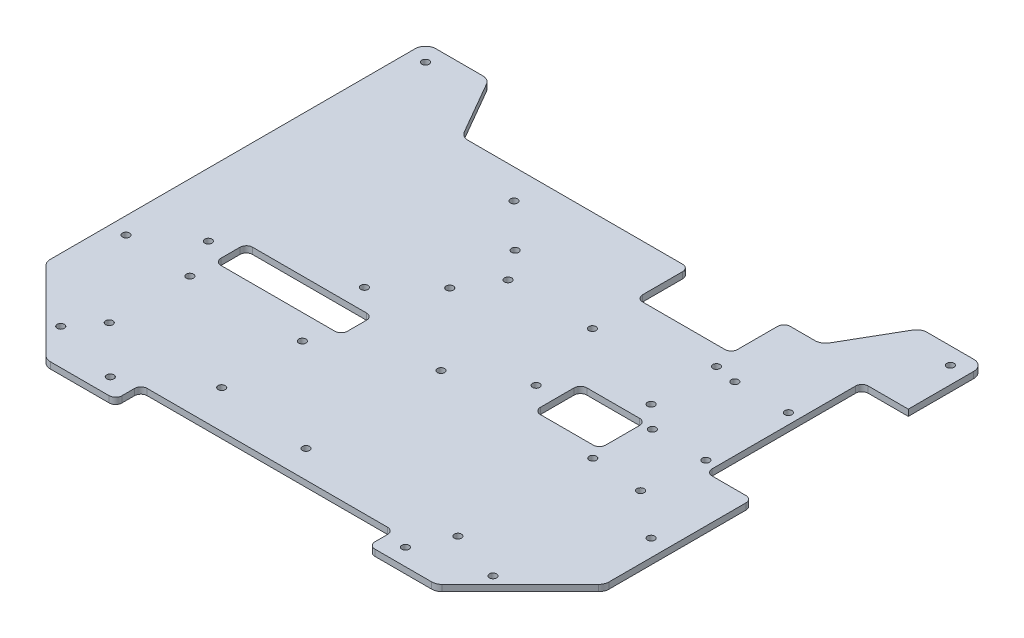
SolidWorks part; units mm, degrees
material "Acier non allié"
ref_plane "Front" through (0, 0, 0) normal (0, 0, 1) x (1, 0, 0)
ref_plane "Top" through (0, 0, 0) normal (0, 1, 0) x (1, 0, 0)
ref_plane "Right" through (0, 0, 0) normal (1, 0, 0) x (0, 0, -1)
sketch "Esquisse1" plane through (0, 0, 0) normal (0, 1, 0) x (1, 0, 0)
  line L0 (0, 0) -> (0, 190) construction
  line L1 (-92.5, 0) -> (92.5, 0)
  line L2 (92.5, 0) -> (132.5, 40)
  line L3 (132.5, 40) -> (132.5, 220)
  line L4 (132.5, 220) -> (102.5, 220)
  line L5 (102.5, 220) -> (85.1795, 190)
  line L6 (85.1795, 190) -> (-85.1795, 190)
  line L7 (-102.5, 220) -> (-85.1795, 190)
  line L8 (-132.5, 220) -> (-102.5, 220)
  line L9 (-132.5, 40) -> (-132.5, 220)
  line L10 (-92.5, 0) -> (-132.5, 40)
  dimension "D1" = 132.5
  dimension "D2" = 220
  dimension "D3" = 60
  dimension "D4" = 30
  dimension "D5" = 40
  dimension "D6" = 40
  dimension "D7" = 30
extrude "Boss.-Extru.1" add sketch "Esquisse1" along normal blind 3
fillet "Congé1" radius 5 10 edges at (92.5, 1.5, 0) (132.5, 1.5, -40) (132.5, 1.5, -220) (102.5, 1.5, -220) (85.1795, 1.5, -190) (-85.1795, 1.5, -190) (-102.5, 1.5, -220) (-132.5, 1.5, -220) (-92.5, 1.5, 0) (-132.5, 1.5, -40)
sketch "Esquisse2" plane through (0, 3, 0) normal (0, 1, 0) x (1, 0, 0)
  line L0 (0, 0) -> (0, 294.1173) construction
  line L2 (-90.4289, 0) -> (90.4289, 0) construction
  circle A0 centre (70, 8) radius 1
  circle A1 centre (124.5, 70) radius 1
  circle A2 centre (124.5, 212) radius 1
  circle A3 centre (-124.5, 212) radius 1
  circle A4 centre (-124.5, 70) radius 1
  circle A5 centre (-70, 8) radius 1
  dimension "D2" = 2
  dimension "D6" = 2
  dimension "D9" = 2
  dimension "D1" = 70
  dimension "D3" = 8
  dimension "D4" = 124.5
  dimension "D5" = 70
  dimension "D7" = 124.5
  dimension "D8" = 212
extrude "Enlèv. mat.-Extru.1" cut sketch "Esquisse2" against normal blind 3
hole_wizard "Dégagement M31" positions "Esquisse3" profile "Esquisse4" hole size "M3" standard "ISO" end condition through all
sketch "Esquisse3" plane through (0, 3, 0) normal (0, 1, 0) x (1, 0, 0)
  point P0 (70, 8)
  point P3 (-70, 8)
  point P6 (-124.5, 70)
  point P9 (-124.5, 212)
  point P12 (124.5, 212)
  point P15 (124.5, 70)
sketch "Esquisse4" plane through (70, 3, -8) normal (1, 0, 0) x (0, 0, 1)
  line L0 (0, 0) -> (0, 3)
  line L1 (0, 3) -> (1.7, 3)
  line L2 (1.7, 3) -> (1.7, 0)
  line L5 (1.7, 0) -> (0, 0)
  line L11 (0, -6.35) -> (0, 107.95) construction
  dimension "Diamètre du perçage jusqu'au prochain" = 3.4
  dimension "Profondeur du perçage jusqu'au prochain" = 3
sketch "Esquisse5" plane through (0, 3, 0) normal (0, 1, 0) x (1, 0, 0)
  line L0 (82.2927, 190) -> (-82.2927, 190) construction
  line L1 (67.5, 190) -> (22.5, 190)
  line L2 (67.5, 190) -> (67.5, 165)
  line L3 (67.5, 165) -> (22.5, 165)
  line L4 (22.5, 190) -> (22.5, 165)
  line L5 (132.5, 42.0711) -> (132.5, 215) construction
  line L6 (132.5, 184) -> (110.5, 184)
  line L7 (132.5, 184) -> (132.5, 110)
  line L8 (132.5, 110) -> (110.5, 110)
  line L9 (110.5, 184) -> (110.5, 110)
  line L10 (127.5, 220) -> (105.3868, 220) construction
  dimension "D1" = 25
  dimension "D2" = 65
  dimension "D3" = 110
  dimension "D4" = 36
  dimension "D5" = 110
  dimension "D6" = 22
extrude "Enlèv. mat.-Extru.2" cut sketch "Esquisse5" against normal through all
fillet "Congé2" radius 3 7 edges at (132.5, 1.5, -110) (110.5, 1.5, -110) (110.5, 1.5, -184) (67.5, 1.5, -190) (67.5, 1.5, -165) (22.5, 1.5, -165) (22.5, 1.5, -190)
sketch "Esquisse6" plane through (0, 3, 0) normal (0, 1, 0) x (1, 0, 0)
  line L0 (110.5, 140.5) -> (-167.6757, 140.5) construction
  line L1 (110.5, 181) -> (110.5, 113) construction
  line L2 (-90.4289, 0) -> (90.4289, 0) construction
  line L3 (110.5, 181) -> (110.5, 113) construction
  circle A0 centre (69.5, 156) radius 1
  circle A1 centre (-26, 156) radius 1
  circle A2 centre (-46.5, 176) radius 1
  circle A3 centre (69.5, 125) radius 1
  circle A4 centre (-26, 125) radius 1
  circle A5 centre (-46.5, 105) radius 1
  dimension "D4" = 2
  dimension "D6" = 2
  dimension "D10" = 2
  dimension "D1" = 140.5
  dimension "D2" = 41
  dimension "D3" = 15.5
  dimension "D5" = 136.5
  dimension "D7" = 15.5
  dimension "D8" = 35.5
  dimension "D9" = 157
extrude "Enlèv. mat.-Extru.3" cut sketch "Esquisse6" against normal through all
hole_wizard "Dégagement M32" positions "Esquisse7" profile "Esquisse8" hole size "M3" standard "ISO"
sketch "Esquisse7" plane through (0, 3, 0) normal (0, 1, 0) x (1, 0, 0)
  point P0 (-46.5, 105)
  point P3 (-26, 125)
  point P6 (-26, 156)
  point P9 (-46.5, 176)
  point P12 (69.5, 156)
  point P15 (69.5, 125)
sketch "Esquisse8" plane through (-46.5, 3, -105) normal (1, 0, 0) x (0, 0, 1)
  line L0 (0, 0) -> (0, 11.0215)
  line L1 (0, 11.0215) -> (1.7, 10)
  line L2 (1.7, 10) -> (1.7, 0)
  line L5 (1.7, 0) -> (0, 0)
  line L10 (0, 11.0215) -> (-1.7, 10) construction
  line L11 (0, -6.35) -> (0, 107.95) construction
  dimension "Diamètre du perçage" = 3.4
  dimension "Profondeur du perçage" = 10
  dimension "Angle de pointe" = 118
sketch "Esquisse9" plane through (0, 3, 0) normal (0, 1, 0) x (1, 0, 0)
  line L0 (132.5, 42.0711) -> (132.5, 107) construction
  line L1 (-90.4289, 0) -> (90.4289, 0) construction
  line L2 (-132.5, 215) -> (-132.5, 42.0711) construction
  line L3 (-39.16, 30) -> (-92.5, 30) construction
  line L4 (-39.16, 30) -> (-39.16, 68.24) construction
  line L5 (-39.16, 68.24) -> (-92.5, 68.24) construction
  line L6 (-92.5, 30) -> (-92.5, 68.24) construction
  line L7 (5.84, 25) -> (5.84, 89) construction
  line L8 (25.5, 165) -> (64.5, 165) construction
  line L9 (24.5, 142.1606) -> (-15.5, 142.1606) construction
  line L10 (110.5, 181) -> (110.5, 113) construction
  line L11 (113.5, 110) -> (129.5, 110) construction
  circle A0 centre (105.5, 115) radius 1
  circle A3 centre (105.5, 154.12) radius 1
  circle A6 centre (-92.5, 68.24) radius 1
  circle A7 centre (-39.16, 68.24) radius 1
  circle A8 centre (-39.16, 30) radius 1
  circle A9 centre (-92.5, 30) radius 1
  circle A10 centre (5.84, 89) radius 1
  circle A11 centre (77.84, 89) radius 1
  circle A12 centre (5.84, 25) radius 1
  circle A13 centre (77.84, 25) radius 1
  circle A14 centre (-15.5, 142.1606) radius 1
  circle A15 centre (24.5, 142.1606) radius 1
  circle A16 centre (34.5, 105.5) radius 1
  circle A17 centre (80.1, 115) radius 1
  circle A18 centre (80.1, 154.12) radius 1
  dimension "D2" = 2
  dimension "D4" = 2
  dimension "D17" = 2
  dimension "D18" = 2
  dimension "D19" = 2
  dimension "D20" = 2
  dimension "D21" = 2
  dimension "D22" = 2
  dimension "D23" = 2
  dimension "D24" = 2
  dimension "D32" = 2
  dimension "D33" = 2
  dimension "D34" = 2
  dimension "D11" = 2
  dimension "D12" = 2
  dimension "D5" = 27
  dimension "25" = 27
  dimension "D10" = 39.12
  dimension "D13" = 38.24
  dimension "D14" = 53.34
  dimension "D15" = 30
  dimension "D16" = 40
  dimension "D25" = 72
  dimension "D26" = 72
  dimension "D27" = 64
  dimension "D28" = 64
  dimension "D29" = 45
  dimension "D30" = 25
  dimension "D31" = 25
  dimension "D36" = 38
  dimension "D37" = 40
  dimension "D39" = 10
  dimension "D7" = 5
  dimension "D8" = 25.4
  dimension "D9" = 25.4
  dimension "D40" = 39.12
  dimension "D35" = 59.5
  dimension "D38" = 76
extrude "Enlèv. mat.-Extru.4" cut sketch "Esquisse9" against normal through all
hole_wizard "Dégagement M33" positions "Esquisse10" profile "Esquisse11" hole size "M3" standard "ISO"
sketch "Esquisse10" plane through (0, 3, 0) normal (0, 1, 0) x (1, 0, 0)
  point P3 (105.5, 115)
  point P9 (105.5, 154.12)
  point P14 (80.1, 154.12)
  point P17 (80.1, 115)
sketch "Esquisse11" plane through (105.5, 3, -115) normal (1, 0, 0) x (0, 0, 1)
  line L0 (0, 0) -> (0, 11.0215)
  line L1 (0, 11.0215) -> (1.7, 10)
  line L2 (1.7, 10) -> (1.7, 0)
  line L5 (1.7, 0) -> (0, 0)
  line L10 (0, 11.0215) -> (-1.7, 10) construction
  line L11 (0, -6.35) -> (0, 107.95) construction
  dimension "Diamètre du perçage" = 3.4
  dimension "Profondeur du perçage" = 10
  dimension "Angle de pointe" = 118
sketch "Esquisse12" plane through (0, 3, 0) normal (0, 1, 0) x (1, 0, 0)
  line L2 (-90.4289, 0) -> (90.4289, 0) construction
  line L3 (102.5, 17) -> (-102.5, 17) construction
  line L4 (102.5, 17) -> (102.5, 87) construction
  line L5 (102.5, 87) -> (-102.5, 87) construction
  line L6 (-102.5, 17) -> (-102.5, 87) construction
  line L7 (132.5, 42.0711) -> (132.5, 107) construction
  circle A4 centre (-102.5, 87) radius 1
  circle A5 centre (102.5, 87) radius 1
  circle A6 centre (102.5, 17) radius 1
  circle A7 centre (-102.5, 17) radius 1
  point P6 (102.5, 52)
  dimension "D5" = 2
  dimension "D6" = 2
  dimension "D7" = 2
  dimension "D8" = 2
  dimension "D1" = 70
  dimension "D2" = 205
  dimension "D3" = 17
  dimension "D4" = 30
extrude "Enlèv. mat.-Extru.5" cut sketch "Esquisse12" against normal through all and the other way through all
hole_wizard "Dégagement M34" positions "Esquisse13" profile "Esquisse14" hole size "M3" standard "ISO"
sketch "Esquisse13" plane through (0, 3, 0) normal (0, 1, 0) x (1, 0, 0)
  point P3 (-92.5, 68.24)
  point P6 (-92.5, 30)
  point P9 (-39.16, 30)
  point P12 (-39.16, 68.24)
  point P16 (5.84, 25)
  point P19 (77.84, 25)
  point P22 (5.84, 89)
  point P25 (77.84, 89)
  point P29 (34.5, 105.5)
  point P32 (24.5, 142.1606)
  point P35 (-15.5, 142.1606)
sketch "Esquisse14" plane through (-92.5, 3, -68.24) normal (1, 0, 0) x (0, 0, 1)
  line L0 (0, 0) -> (0, 11.0215)
  line L1 (0, 11.0215) -> (1.7, 10)
  line L2 (1.7, 10) -> (1.7, 0)
  line L5 (1.7, 0) -> (0, 0)
  line L10 (0, 11.0215) -> (-1.7, 10) construction
  line L11 (0, -6.35) -> (0, 107.95) construction
  dimension "Diamètre du perçage" = 3.4
  dimension "Profondeur du perçage" = 10
  dimension "Angle de pointe" = 118
hole_wizard "Dégagement M35" positions "Esquisse15" profile "Esquisse16" hole size "M3" standard "ISO"
sketch "Esquisse15" plane through (0, 3, 0) normal (0, 1, 0) x (1, 0, 0)
  point P0 (-102.5, 17)
  point P3 (-102.5, 87)
  point P6 (102.5, 87)
  point P9 (102.5, 17)
sketch "Esquisse16" plane through (-102.5, 3, -17) normal (1, 0, 0) x (0, 0, 1)
  line L0 (0, 0) -> (0, 11.0215)
  line L1 (0, 11.0215) -> (1.7, 10)
  line L2 (1.7, 10) -> (1.7, 0)
  line L5 (1.7, 0) -> (0, 0)
  line L10 (0, 11.0215) -> (-1.7, 10) construction
  line L11 (0, -6.35) -> (0, 107.95) construction
  dimension "Diamètre du perçage" = 3.4
  dimension "Profondeur du perçage" = 10
  dimension "Angle de pointe" = 118
sketch "Esquisse17" plane through (0, 3, 0) normal (0, 1, 0) x (1, 0, 0)
  line L0 (-90.4289, 0) -> (90.4289, 0) construction
  line L1 (-92.5, 95) -> (-32.5, 95)
  line L2 (-92.5, 95) -> (-92.5, 80)
  line L3 (-92.5, 80) -> (-32.5, 80)
  line L4 (-32.5, 95) -> (-32.5, 80)
  line L5 (-132.5, 215) -> (-132.5, 42.0711) construction
  line L6 (132.5, 42.0711) -> (132.5, 107) construction
  line L7 (44.5, 116.5) -> (75.5, 116.5)
  line L8 (44.5, 116.5) -> (44.5, 94.5)
  line L9 (44.5, 94.5) -> (75.5, 94.5)
  line L10 (75.5, 116.5) -> (75.5, 94.5)
  line L11 (82.2927, 190) -> (70.5, 190) construction
  line L13 (-59.5, 12) -> (60.5, 12)
  line L14 (-59.5, 12) -> (-59.5, 0)
  line L15 (-59.5, 0) -> (60.5, 0)
  line L16 (60.5, 12) -> (60.5, 0)
  dimension "D1" = 60
  dimension "D2" = 15
  dimension "D3" = 80
  dimension "D4" = 40
  dimension "D5" = 31
  dimension "D6" = 22
  dimension "D7" = 57
  dimension "D8" = 73.5
  dimension "D9" = 12
  dimension "D11" = 120
  dimension "D12" = 72
extrude "Enlèv. mat.-Extru.6" cut sketch "Esquisse17" against normal up to surface (3 mm away) up to face at (-102.5, 0, -15.3)
fillet "Congé3" radius 3 12 edges at (60.5, 1.5, 0) (60.5, 1.5, -12) (-59.5, 1.5, -12) (-59.5, 1.5, 0) (44.5, 1.5, -116.5) (75.5, 1.5, -116.5) (75.5, 1.5, -94.5) (44.5, 1.5, -94.5) (-92.5, 1.5, -80) (-32.5, 1.5, -80) (-32.5, 1.5, -95) (-92.5, 1.5, -95)
equation "\"WIDTH\"= 300mm'Total width of the robot"
equation "\"LENGTH\"= 220mm'Total length of the robot"
equation "\"CUT_DEPTH\"= 45mm'Depth of the cut on the edges of the plate"
equation "\"Plate_th\"= 3mm'Thickness of the plate"
equation "\"D1\"= \"Plate_th\""
equation "\"D5@Esquisse9\"=\"25@Esquisse9\""
